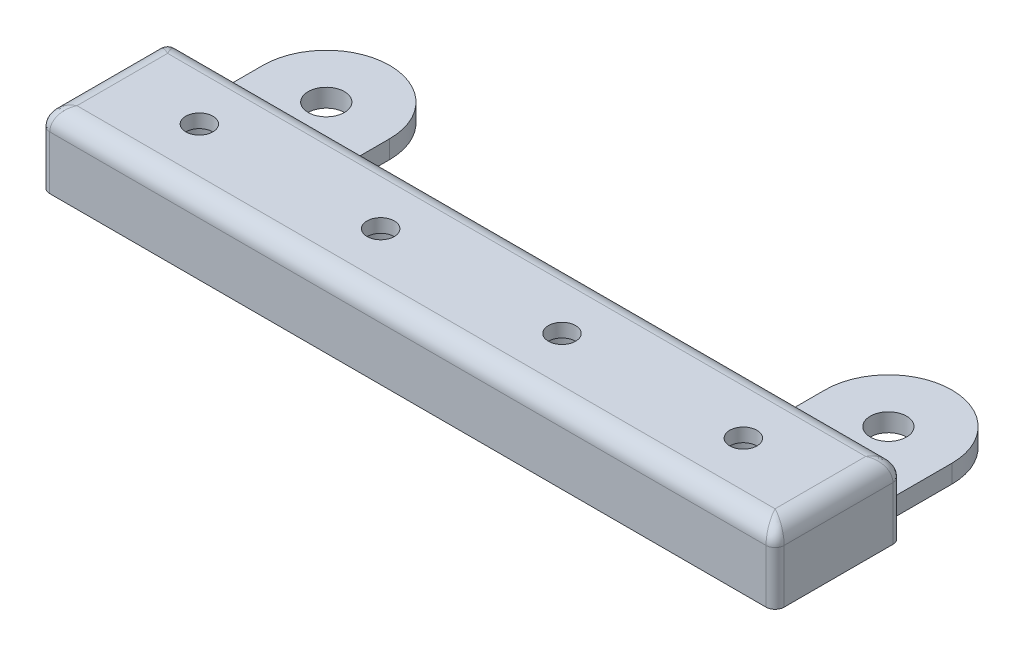
SolidWorks part; units mm, degrees
ref_plane "Front Plane" through (0, 0, 0) normal (0, 0, 1) x (1, 0, 0)
ref_plane "Top Plane" through (0, 0, 0) normal (0, 1, 0) x (1, 0, 0)
ref_plane "Right Plane" through (0, 0, 0) normal (1, 0, 0) x (0, 0, -1)
sketch "Sketch1" plane through (0, 0, 0) normal (0, 1, 0) x (1, 0, 0)
  line L1 (0, 0) -> (77, 0)
  line L2 (0, 0) -> (0, 10)
  line L3 (0, 10) -> (77, 10)
  line L4 (77, 0) -> (77, 10)
  line L5 (-2, 12) -> (79, 12)
  line L6 (-2, 12) -> (-2, -2)
  line L7 (-2, -2) -> (79, -2)
  line L8 (79, 12) -> (79, -2)
  dimension "D1" = 77
  dimension "D2" = 10
  dimension "D3" = 2
  dimension "D4" = 2
  dimension "D5" = 2
  dimension "D6" = 2
extrude "Boss-Extrude1" add sketch "Sketch1" along normal blind 1.9
sketch "Sketch3" plane through (0, 1.9, 0) normal (0, 1, 0) x (1, 0, 0)
  line L1 (-2, 12) -> (79, 12)
  line L2 (-2, 12) -> (-2, -2)
  line L3 (-2, -2) -> (79, -2)
  line L4 (79, 12) -> (79, -2)
extrude "Boss-Extrude2" add sketch "Sketch3" along normal blind 6
sketch "Sketch4" plane through (0, 1.9, 0) normal (0, -1, 0) x (1, 0, 0)
  line L0 (0, -10) -> (0, 0) construction
  line L1 (0, 0) -> (77, 0) construction
  circle A0 centre (8.5, -5) radius 2.75
  circle A1 centre (28.5, -5) radius 2.75
  circle A2 centre (48.5, -5) radius 2.75
  circle A3 centre (68.5, -5) radius 2.75
  circle A8 centre (148.5, -5) radius 2.75 [skipped]
  circle A9 centre (128.5, -5) radius 2.75 [skipped]
  circle A10 centre (108.5, -5) radius 2.75 [skipped]
  circle A11 centre (88.5, -5) radius 2.75 [skipped]
  dimension "D1" = 5.5
  dimension "D2" = 8.5
  dimension "D3" = 5
  dimension "D4" = 8
extrude "Cut-Extrude1" cut sketch "Sketch4" against normal blind 4.5
sketch "Sketch5" plane through (0, 6.4, 0) normal (0, -1, 0) x (1, 0, 0)
  circle A0 centre (8.5, -5) radius 1.5
  circle A1 centre (28.5, -5) radius 1.5
  circle A2 centre (48.5, -5) radius 1.5
  circle A3 centre (68.5, -5) radius 1.5
  circle A8 centre (108.5, -5) radius 1.5 [skipped]
  circle A9 centre (128.5, -5) radius 1.5 [skipped]
  circle A10 centre (148.5, -5) radius 1.5 [skipped]
  circle A11 centre (88.5, -5) radius 1.5 [skipped]
  dimension "D1" = 3
  dimension "D2" = 8
extrude "Cut-Extrude2" cut sketch "Sketch5" against normal up to next
sketch "Sketch6" plane through (0, 0, 0) normal (0, -1, 0) x (1, 0, 0)
  line L0 (0, -10) -> (0, 0) construction
  line L1 (38.5, 0) -> (38.5, -10) construction
  line L2 (0, 0) -> (77, 0) construction
  line L3 (77, -10) -> (0, -10) construction
  line L4 (0.5, -20) -> (0.5, -12)
  line L5 (79, -12) -> (-2, -12) construction
  line L6 (14.5, -20) -> (14.5, -12)
  line L7 (62.5, -20) -> (62.5, -12)
  line L8 (76.5, -20) -> (76.5, -12)
  circle A1 centre (7.5, -20) radius 2
  circle A2 centre (7.5, -20) radius 7
  circle A5 centre (8.5, -5) radius 1.5 construction
  circle A6 centre (69.5, -20) radius 7
  circle A7 centre (69.5, -20) radius 2
  line M9 (-2, -12) -> (79, -12)
  dimension "D2" = 4
  dimension "D3" = 5
  dimension "D5" = 15
  dimension "D6" = 7.5
extrude "Boss-Extrude3" add sketch "Sketch6" against normal blind 2 contours A6 A7 M9 | L7 A6 M9 | A6 L8 M9 | A2 L6 M9 | A2 A1 M9 | A2 L4 M9 region at (69.5, 0, -12.1612) region at (0.6612, 0, -16) region at (7.5, 0, -13.198) region at (69.5, 0, -13.198)
fillet "Fillet3" radius 1 8 edges at (0.5, 1, -12) (-2, 3.95, -12) (-2, 3.95, 2) (14.5, 1, -12) (79, 3.95, 2) (62.5, 1, -12) (76.5, 1, -12) (79, 3.95, -12)
fillet "Fillet4" radius 2 10 edges at (78.7071, 7.9, -11.7071) (79, 7.9, -5) (78.7071, 7.9, 1.7071) (38.5, 7.9, 2) (-1.7071, 7.9, 1.7071) (-2, 7.9, -5) (-1.7071, 7.9, -11.7071) (7.5, 2, -12) (69.5, 2, -12) (38.5, 7.9, -12)
